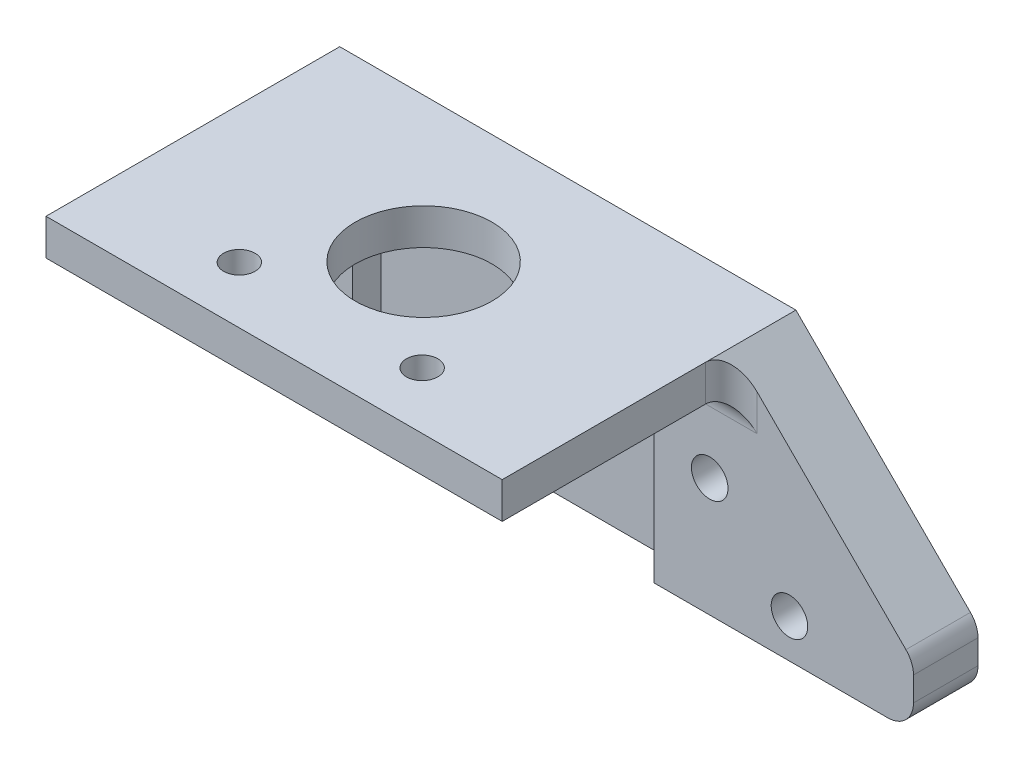
SolidWorks part; units mm, degrees
other "Markup1"
sketch "Sketch16" plane through (-39.1905, -20.3674, 24.05) normal (-0.0308, -0.9994, 0.0158) x (0.9994, -0.0306, 0.0156)
material "Alloy Steel"
ref_plane "Front Plane" through (0, 0, 0) normal (0, 0, 1) x (1, 0, 0)
ref_plane "Top Plane" through (0, 0, 0) normal (0, 1, 0) x (1, 0, 0)
ref_plane "Right Plane" through (0, 0, 0) normal (1, 0, 0) x (0, 0, -1)
ref_plane "Plane1" through (0, 0, 5) normal (0, 0, 1) x (1, 0, 0)
sketch "Sketch1" plane through (0, 0, 5) normal (0, 0, 1) x (1, 0, 0)
  line L0 (-21.1834, 0) -> (-21.1834, -8.8135)
  line L1 (-19.5308, -15.2763) -> (24.6825, -15.2763)
  line L2 (24.6825, -14.2126) -> (23.7179, 0)
  line L3 (23.7179, 0) -> (23.7179, 4.989)
  line L4 (23.7179, 4.989) -> (-21.1834, 4.989)
  line L5 (-21.1834, 4.989) -> (-21.1834, 0)
  arc A0 (-21.1834, -8.8135) -> (-19.5308, -15.2763) centre (-19.5308, -11.8336) ccw
  arc A1 (24.6825, -15.2763) -> (24.6825, -14.2126) centre (24.6825, -14.7444) ccw
  dimension "D1" = 44.9013
extrude "Boss-Extrude1" add sketch "Sketch1" against normal blind 1.7859 and the other way blind 1.7859
sketch "Sketch2" plane through (0, 0, 6.7859) normal (0, 0, 1) x (1, 0, 0)
  line L0 (23.77, 0) -> (-21.23, 0)
  line L1 (-21.23, 0) -> (-21.23, 3.5719)
  line L2 (-21.23, 3.5719) -> (23.77, 3.5719)
  line L3 (23.77, 3.5719) -> (23.77, 0)
  dimension "D1" = 3.5719
extrude "Boss-Extrude2" add sketch "Sketch2" along normal blind 25.4
hole_wizard "Ø5.0 (5) Diameter Hole1" [suppressed] positions "Sketch4" profile "Sketch3" hole size "Ø5.0" standard "ANSI Metric"
sketch "Sketch4" plane through (0, 0, 1.4281) normal (0, 0, -1) x (-1, 0, 0)
  point P0 (-20.42, -22.057)
  point P1 (20.42, -22.057)
sketch "Sketch3" plane through (20.42, -22.057, 1.4281) normal (1, 0, 0) x (0, 1, 0)
  line L0 (0, 0) -> (0, 22.6219)
  line L1 (0, 22.6219) -> (2.5, 22.6219)
  line L2 (2.5, 22.6219) -> (2.5, 0)
  line L5 (2.5, 0) -> (0, 0)
  line L11 (0, -6.35) -> (0, 107.95) construction
  dimension "Thru Hole Dia." = 5
  dimension "Thru Hole Depth" = 22.6219
fillet "Fillet1" radius 2 1 edges at (1.2672, 4.989, 3.2141) tangent propagation no
fillet "Fillet2" [suppressed] radius 8
hole_wizard "Ø13.5 (13.5) Diameter Hole1" [suppressed] positions "Sketch6" profile "Sketch5" hole size "Ø13.5" standard "ANSI Metric"
sketch "Sketch6" plane through (0, 4.989, 0) normal (0, 1, 0) x (1, 0, 0)
  line L0 (-55, -5) -> (55, -5) construction
  point P0 (0, -13)
  dimension "D1" = 8
sketch "Sketch5" plane through (0, 4.989, 13) normal (1, 0, 0) x (0, 0, 1)
  line L0 (0, 0) -> (0, 20.2653)
  line L1 (0, 20.2653) -> (6.75, 20.2653)
  line L2 (6.75, 20.2653) -> (6.75, 0)
  line L5 (6.75, 0) -> (0, 0)
  line L11 (0, -6.35) -> (0, 107.95) construction
  dimension "Thru Hole Dia." = 13.5
  dimension "Thru Hole Depth" = 20.2653
hole_wizard "Ø5.0 (5) Diameter Hole2" [suppressed] positions "Sketch8" profile "Sketch7" hole size "Ø5.0" standard "ANSI Metric"
sketch "Sketch8" plane through (0, 4.989, 0) normal (0, 1, 0) x (1, 0, 0)
  line L0 (-55, -5) -> (55, -5) construction
  point P0 (-12, -17.51)
  point P1 (12, -17.51)
  dimension "D1" = 12.51
  dimension "D2" = 12.51
  dimension "D3" = 12
  dimension "D4" = 24
sketch "Sketch7" plane through (-12, 4.989, 17.51) normal (1, 0, 0) x (0, 0, 1)
  line L0 (0, 0) -> (0, 20.2653)
  line L1 (0, 20.2653) -> (2.5, 20.2653)
  line L2 (2.5, 20.2653) -> (2.5, 0)
  line L5 (2.5, 0) -> (0, 0)
  line L11 (0, -6.35) -> (0, 107.95) construction
  dimension "Thru Hole Dia." = 5
  dimension "Thru Hole Depth" = 20.2653
sketch "Sketch9" plane through (0, 0, 6.7859) normal (0, 0, 1) x (1, 0, 0)
  line L1 (-21.1834, 3.5719) -> (23.7179, 3.5719)
  line L2 (-21.1834, 3.5719) -> (-21.1834, 4.989)
  line L3 (-21.1834, 4.989) -> (23.7179, 4.989)
  line L4 (23.7179, 3.5719) -> (23.7179, 4.989)
extrude "Cut-Extrude1" cut sketch "Sketch9" against normal blind 10
sketch "Sketch10" plane through (0, 0, 6.7859) normal (0, 0, 1) x (1, 0, 0)
  line L0 (29.4905, -16.975) -> (14.2053, -1.6897) construction
  line L1 (-21.1834, 0) -> (23.7179, 0) construction
  line L2 (-25.6987, -15.2653) -> (-15.0019, -4.5684) construction
  circle A0 centre (21.6238, -9.1082) radius 1.8034
  circle A1 centre (-19.0029, -8.5694) radius 1.8034
  circle A2 centre (29.4905, -16.975) radius 1.8714
  circle A3 centre (-25.6987, -15.2653) radius 1.7313
  dimension "D1" = 3.6068
  dimension "D2" = 3.6068
  dimension "D3" = 135
  dimension "D4" = 11.1252
  dimension "D5" = 135
  dimension "D6" = 29.3487
extrude "Cut-Extrude2" [suppressed] cut sketch "Sketch10" against normal through all
sketch "Sketch11" plane through (0, 0, 6.7859) normal (0, 0, 1) x (1, 0, 0)
  line L0 (-19.5308, -15.2763) -> (24.6825, -15.2763) construction
  line L1 (-8.1008, -15.2763) -> (10.9492, -15.2763)
  line L2 (-8.1008, -15.2763) -> (-8.1008, -7.3607)
  line L3 (-8.1008, -7.3607) -> (10.9492, -7.3607)
  line L4 (10.9492, -15.2763) -> (10.9492, -7.3607)
  dimension "D1" = 19.05
  dimension "D2" = 11.43
extrude "Cut-Extrude3" [suppressed] cut sketch "Sketch11" against normal through all
sketch "Sketch13" plane through (0, 0, 6.7859) normal (0, 0, 1) x (1, 0, 0)
  line L4 (-21.23, 3.5719) -> (-39.1905, -14.3886)
  line L5 (23.77, 3.5719) -> (41.7305, -14.3886)
  line L6 (-39.1905, -14.3886) -> (-39.1905, -20.3674)
  line L8 (23.77, 0) -> (23.77, 3.5719)
  line L9 (23.77, 3.5719) -> (-21.23, 3.5719)
  line L10 (-21.23, 3.5719) -> (-21.23, 0)
  line L11 (-21.23, 0) -> (23.77, 0)
  line L13 (23.77, 3.5719) -> (-21.23, 3.5719)
  line L19 (-39.1905, -20.3674) -> (41.7305, -20.3674)
  line L20 (41.7305, -20.3674) -> (41.7305, -14.3886)
  dimension "D1" = 135
  dimension "D2" = 135
  dimension "D3" = 25.4
  dimension "D4" = 0
extrude "Boss-Extrude3" add sketch "Sketch13" against normal through all
sketch "Sketch14" plane through (0, 0, 6.7859) normal (0, 0, 1) x (1, 0, 0)
  line L0 (-21.23, 3.5719) -> (-39.1905, -14.3886) construction
  line L2 (-21.23, 3.5719) -> (-39.1905, -14.3886) construction
  line L3 (-26.9594, -16.5259) -> (-34.1436, -9.3417) construction
  line L4 (41.7305, -14.3886) -> (23.77, 3.5719) construction
  line L5 (29.4994, -16.5259) -> (36.6836, -9.3417) construction
  circle A0 centre (-26.9594, -16.5259) radius 2.4384
  circle A1 centre (-19.0927, -8.6592) radius 2.4384
  circle A2 centre (21.6327, -8.6592) radius 2.4384
  circle A3 centre (29.4994, -16.5259) radius 2.4384
  dimension "D1" = 10.16
  dimension "D5" = 4.8768
  dimension "D6" = 4.8768
  dimension "D8" = 4.8768
  dimension "D9" = 4.8768
  dimension "D2" = 7.1374
  dimension "D3" = 11.1252
  dimension "D4" = 10.16
  dimension "D7" = 10.16
  dimension "D10" = 11.1252
  dimension "D11" = 7.1374
  dimension "D12" = 10.16
extrude "Cut-Extrude4" cut sketch "Sketch14" against normal through all
sketch "Sketch15" plane through (0, 0, 0) normal (0, -1, 0) x (1, 0, 0)
  line L0 (-21.23, 19.4859) -> (23.77, 19.4859) construction
  line L3 (-21.23, 32.1859) -> (-21.23, 6.7859) construction
  line L4 (23.77, 32.1859) -> (23.77, 6.7859) construction
  line L5 (-39.1905, 3.2141) -> (41.7305, 3.2141) construction
  circle A0 centre (1.27, 17.4381) radius 6.75
  circle A1 centre (-7.764, 26.5821) radius 1.55
  circle A2 centre (10.27, 26.5821) radius 1.55
  point P5 (-21.23, 14.525)
  point P9 (1.27, 19.4859)
  dimension "D1" = 13.5
  dimension "D2" = 3.1
  dimension "D3" = 3.1
  dimension "D4" = 9
  dimension "D5" = 9.144
  dimension "D6" = 18.034
  dimension "D7" = 14.224
extrude "Cut-Extrude5" cut sketch "Sketch15" against normal through all and the other way through all
sketch "Sketch17" plane through (0, 3.5719, 0) normal (0, 1, 0) x (1, 0, 0)
  line L0 (23.77, -3.2141) -> (-21.23, -3.2141) construction
  line L1 (-10.795, -3.2141) -> (10.795, -3.2141)
  line L2 (-10.795, -3.2141) -> (-10.795, -0.6741)
  line L3 (-10.795, -0.6741) -> (10.795, -0.6741)
  line L4 (10.795, -3.2141) -> (10.795, -0.6741)
  point P8 (0, -0.6741)
  dimension "D1" = 21.59
  dimension "D2" = 2.54
extrude "Boss-Extrude4" [suppressed] add sketch "Sketch17" against normal through all
sketch "Sketch18" [suppressed] plane through (0, 0, 0.6741) normal (0, 0, -1) x (-1, 0, 0)
  line L0 (-10.795, 3.5719) -> (-18.415, -20.3674)
  line L1 (-10.795, -20.3674) -> (-39.1905, -20.3674) construction
  line L2 (-18.415, -20.3674) -> (-10.795, -20.3674)
  line L3 (-10.795, -20.3674) -> (-10.795, 3.5719)
  line L4 (10.795, 3.5719) -> (10.795, -20.3674)
  line L5 (10.795, -20.3674) -> (18.415, -20.3674)
  line L6 (36.6505, -20.3674) -> (10.795, -20.3674) construction
  line L7 (18.415, -20.3674) -> (10.795, 3.5719)
  dimension "D1" = 7.62
  dimension "D2" = 7.62
extrude "Boss-Extrude5" [suppressed] add sketch "Sketch18" against normal up to next
sketch "Sketch19" plane through (0, 0, 6.7859) normal (0, 0, 1) x (1, 0, 0)
  line L0 (-39.1905, -14.3886) -> (-21.23, 3.5719)
  line L1 (-21.23, 3.5719) -> (-21.23, 0)
  line L2 (-21.23, 0) -> (-13.61, 0)
  line L3 (-21.23, 0) -> (23.77, 0) construction
  line L4 (-13.61, 0) -> (-13.61, -20.3674)
  line L5 (-39.1905, -20.3674) -> (41.7305, -20.3674) construction
  line L6 (-13.61, -20.3674) -> (-39.1905, -20.3674)
  line L7 (-39.1905, -20.3674) -> (-39.1905, -14.3886)
  line L8 (41.7305, -20.3674) -> (41.7305, -14.3886)
  line L9 (41.7305, -14.3886) -> (23.77, 3.5719)
  line L10 (23.77, 3.5719) -> (23.77, 0)
  line L11 (23.77, 0) -> (16.15, 0)
  line L12 (16.15, 0) -> (16.15, -20.3674)
  line L13 (16.15, -20.3674) -> (41.7305, -20.3674)
  circle A0 centre (-19.0927, -8.6592) radius 1.8034
  circle A1 centre (-26.9594, -16.5259) radius 1.8034
  circle A2 centre (21.6327, -8.6592) radius 1.8034
  circle A3 centre (29.4994, -16.5259) radius 1.8034
  dimension "D1" = 7.62
  dimension "D2" = 7.62
extrude "Boss-Extrude6" add sketch "Sketch19" along normal blind 2.794
fillet "Fillet3" radius 2.54 11 edges at (-13.61, 0, 8.1829) (16.15, 0, 8.1829) (1.27, 0, 6.7859) (19.96, 0, 9.5799) (23.77, 1.7859, 9.5799) (-17.42, 0, 9.5799) (-21.23, 1.7859, 9.5799) (41.7305, -14.3886, 6.397) (41.7305, -20.3674, 6.397) (-39.1905, -14.3886, 6.397) (-39.1905, -20.3674, 6.397)
